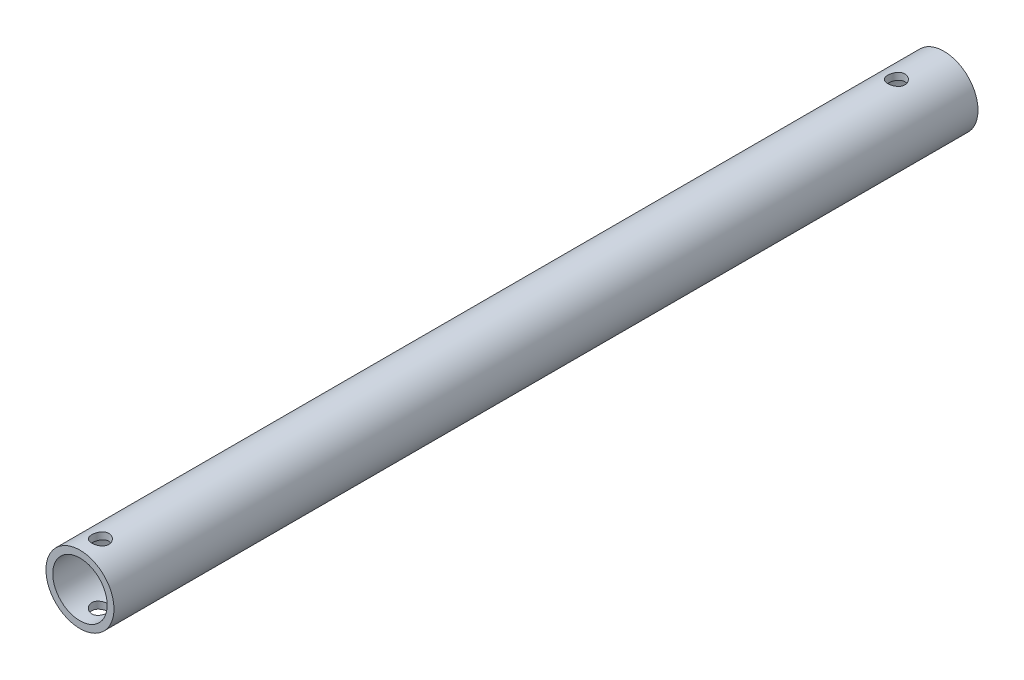
SolidWorks part; units mm, degrees
ref_plane "Front Plane" through (0, 0, 0) normal (0, 0, 1) x (1, 0, 0)
ref_plane "Top Plane" through (0, 0, 0) normal (0, 1, 0) x (1, 0, 0)
ref_plane "Right Plane" through (0, 0, 0) normal (1, 0, 0) x (0, 0, -1)
sketch "Sketch1" plane through (0, 0, 0) normal (0, 0, 1) x (1, 0, 0)
  line L0 (-15.875, 0) -> (15.875, 0) construction
  line L1 (0, -15.875) -> (0, 15.875) construction
  circle A0 centre (0, 0) radius 15.875
  circle A1 centre (0, 0) radius 12.7
  point P4 (0, 0)
  point P9 (0, 0)
  point P10 (12.7, 0)
  dimension "ID" = 25.4
  dimension "OD" = 31.75
  dimension "Wall Thickness" = 3.175
sketch "Sketch2" plane through (0, 0, 0) normal (1, 0, 0) x (0, 0, -1)
  line L0 (457.2, 15.875) -> (-457.2, 15.875) construction
  line L1 (0, 15.875) -> (0, -15.875) construction
  point P3 (-381, 15.875)
  point P4 (0, 15.875)
  point P5 (381, 15.875)
  dimension "D2" = 76.2
  dimension "Length" = 914.4
sketch "Sketch3" plane through (0, 0, 0) normal (0, 0, 1) x (1, 0, 0)
  line L0 (0, -15.875) -> (0, 15.875) construction
  circle A0 centre (0, 0) radius 15.875
  circle A1 centre (0, 0) radius 12.7
  circle A2 centre (0, 0) radius 12.7 construction
extrude "Boss-Extrude1" add sketch "Sketch3" along normal mid plane 914.4
sketch "Sketch4" plane through (0, 0, 457.2) normal (0, 0, 1) x (1, 0, 0)
  circle A0 centre (0, 0) radius 24.6875
extrude "Cut-Extrude1" cut sketch "Sketch4" against normal offset from surface (511.175 mm away) 403.225 up to face at (15.875, 0, -457.2)
sketch "Sketch5" plane through (0, 0, 0) normal (0, 1, 0) x (1, 0, 0)
  line L0 (-15.875, 53.975) -> (15.875, 53.975) construction
  line L1 (0, 63.5) -> (-15.875, 63.5) construction
  line L2 (-15.875, 457.2) -> (-15.875, 53.975) construction
  line L3 (0, 63.5) -> (15.875, 63.5) construction
  line L4 (15.875, 53.975) -> (15.875, 457.2) construction
  circle A0 centre (0, 63.5) radius 3.9687
  circle A1 centre (0, 434.975) radius 3.9688
  dimension "D1" = 7.9375
  dimension "D3" = 7.9375
  dimension "D2" = 9.525
  dimension "D4" = 381
extrude "Cut-Extrude2" cut sketch "Sketch5" against normal through all both and the other way through all
equation "\"D1@Boss-Extrude1\" = \"Length@Sketch2\""
equation "\"D2@Sketch2\"=\"D1@Sketch2\""
